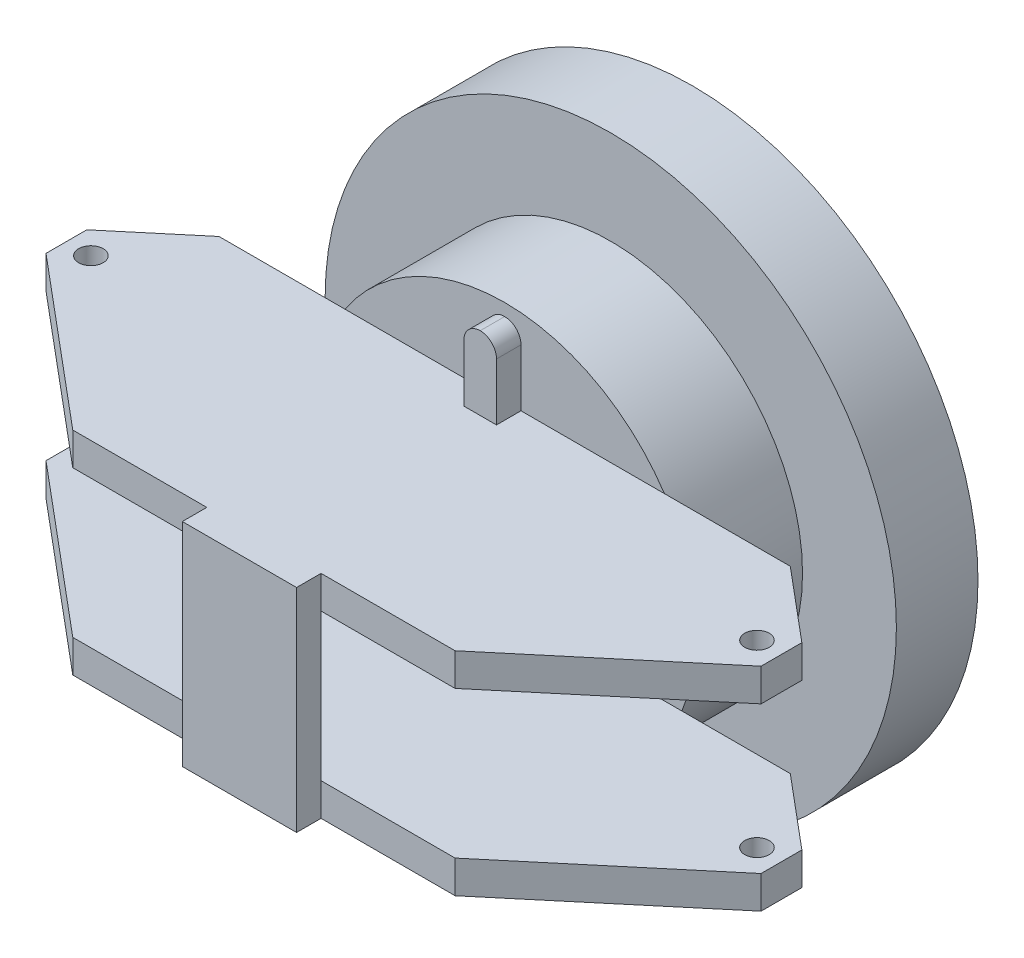
SolidWorks part; units mm, degrees
ref_plane "Front Plane" through (0, 0, 0) normal (0, 0, 1) x (1, 0, 0)
ref_plane "Top Plane" through (0, 0, 0) normal (0, 1, 0) x (1, 0, 0)
ref_plane "Right Plane" through (0, 0, 0) normal (1, 0, 0) x (0, 0, -1)
sketch "Sketch1" plane through (0, 0, 0) normal (0, 0, 1) x (1, 0, 0)
  circle A0 centre (0, 0) radius 35
  dimension "D1" = 70
extrude "Boss-Extrude1" add sketch "Sketch1" along normal blind 10
sketch "Sketch2" plane through (0, 0, 10) normal (0, 0, 1) x (1, 0, 0)
  circle A0 centre (0, 0) radius 23.5
  dimension "D1" = 47
extrude "Boss-Extrude2" add sketch "Sketch2" along normal blind 13
ref_plane "Plane1" through (0, 13, 0) normal (0, 1, 0) x (1, 0, 0)
sketch "Sketch3" plane through (0, 13, 0) normal (0, 1, 0) x (1, 0, 0)
  line L0 (35, -23) -> (-35, -23)
  line L1 (-23.5, -23) -> (23.5, -23) construction
  line L2 (-35, -23) -> (-43.8095, -30.3921)
  line L3 (-43.8095, -30.3921) -> (-43.8095, -35.3921)
  line L4 (-43.8095, -35.3921) -> (-23.4223, -52.499)
  line L5 (-23.4223, -52.499) -> (23.4223, -52.499)
  line L6 (-43.8095, -35.3921) -> (-43.8095, -43.6451) construction
  line L7 (-35, -23) -> (-23.4223, -52.499) construction
  line L8 (0, -23) -> (0, -52.499) construction
  line L9 (35, -23) -> (23.4223, -52.499) construction
  line L10 (35, -23) -> (43.8095, -30.3921)
  line L11 (43.8095, -35.3921) -> (23.4223, -52.499)
  line L12 (43.8095, -30.3921) -> (43.8095, -35.3921)
  line L13 (-23.4223, -23) -> (-23.4223, -52.499) construction
  line L14 (23.5, -23) -> (23.4223, -52.499) construction
  line L15 (23.5, -23) -> (23.5, -10) construction
  dimension "D1" = 35
  dimension "D2" = 11.5
  dimension "D3" = 140
  dimension "D4" = 5
  dimension "D5" = 50
extrude "Boss-Extrude3" add sketch "Sketch3" against normal blind 4
sketch "Sketch4" plane through (0, 13, 0) normal (0, 1, 0) x (1, 0, 0)
  line L0 (-43.8095, -30.3921) -> (-43.8095, -35.3921) construction
  circle A0 centre (-40.8095, -32.8921) radius 1.5
  point P4 (-43.8095, -32.8921)
  dimension "D2" = 3
  dimension "D1" = 3
extrude "Cut-Extrude1" cut sketch "Sketch4" against normal blind 4
mirror "Mirror1" about plane through (0, 0, 0) normal (1, 0, 0) of "Cut-Extrude1"
mirror "Mirror2" about plane through (0, 0, 0) normal (0, 1, 0) of "Mirror1", "Cut-Extrude1", "Boss-Extrude3"
sketch "Sketch5" plane through (0, 0, 23) normal (0, 0, 1) x (1, 0, 0)
  line L1 (19.5768, -13) -> (-19.5768, -13) construction
  line L2 (0, -13) -> (2, -13)
  line L3 (2, -13) -> (2, -22)
  line L4 (2, -22) -> (0, -22)
  line L5 (0, -22) -> (-2, -22)
  line L6 (-2, -22) -> (-2, -13)
  line L7 (-23.4223, -13) -> (23.4223, -13) construction
  line L8 (-2, -13) -> (0, -13)
  dimension "D3" = 9
  dimension "D4" = 9
extrude "Boss-Extrude4" add sketch "Sketch5" along normal blind 3
fillet "Fillet1" radius 2 2 edges at (-2, -22, 24.5) (2, -22, 24.5)
mirror "Mirror3" about plane through (0, 0, 0) normal (0, 1, 0) of "Fillet1", "Boss-Extrude4"
sketch "Sketch6" plane through (0, 0, 52.499) normal (0, 0, 1) x (1, 0, 0)
  line L0 (19.5768, 13) -> (2, 13) construction
  line L1 (-7, -13) -> (7, -13)
  line L2 (-7, -13) -> (-7, 13)
  line L3 (-7, 13) -> (7, 13)
  line L4 (7, -13) -> (7, 13)
  line L5 (-7, -13) -> (7, 13) construction
  line L6 (-7, 13) -> (7, -13) construction
  point P0 (0, 0)
  dimension "D1" = 14
extrude "Boss-Extrude5" add sketch "Sketch6" along normal blind 3
sketch "Sketch7" plane through (0, 0, 0) normal (0, 0, -1) x (-1, 0, 0)
  circle A0 centre (0, 0) radius 10
  dimension "D1" = 20
extrude "Cut-Extrude3" cut sketch "Sketch7" against normal blind 10
